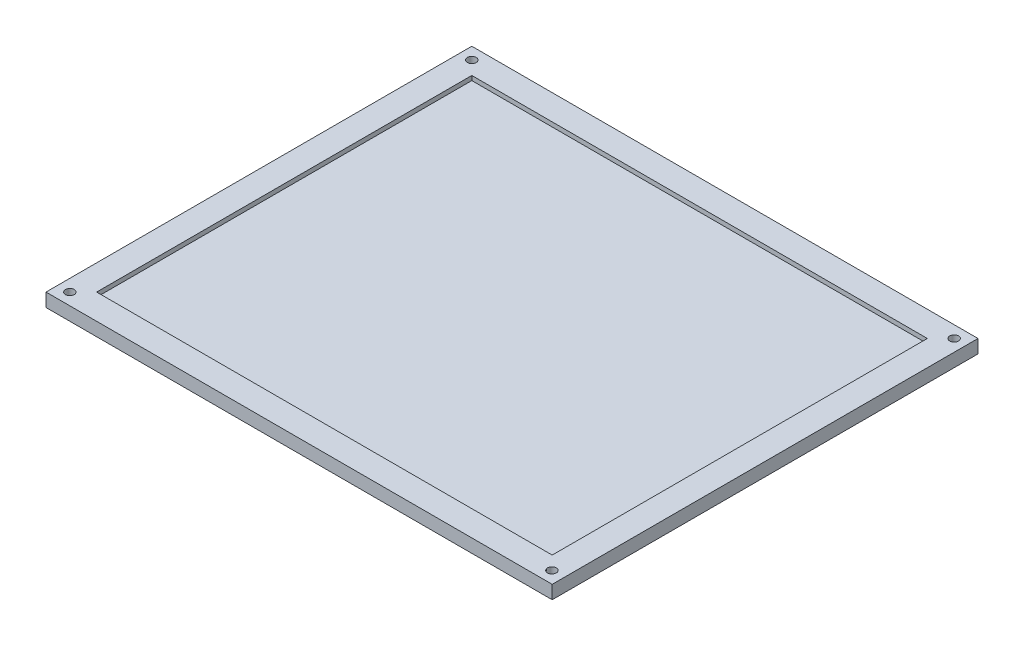
SolidWorks part; units mm, degrees
ref_plane "Front Plane" through (0, 0, 0) normal (0, 0, 1) x (1, 0, 0)
ref_plane "Top Plane" through (0, 0, 0) normal (0, 1, 0) x (1, 0, 0)
ref_plane "Right Plane" through (0, 0, 0) normal (1, 0, 0) x (0, 0, -1)
sketch "Sketch1" plane through (0, 0, 0) normal (0, 1, 0) x (1, 0, 0)
  line L1 (-94.45, 79.45) -> (94.45, 79.45)
  line L2 (-94.45, 79.45) -> (-94.45, -79.45)
  line L3 (-94.45, -79.45) -> (94.45, -79.45)
  line L4 (94.45, 79.45) -> (94.45, -79.45)
  point P4 (0, 79.45)
  point P6 (-94.45, 0)
  dimension "D1" = 158.9
  dimension "D2" = 188.9
extrude "Boss-Extrude1" add sketch "Sketch1" along normal blind 5
sketch "Sketch2" plane through (0, 5, 0) normal (0, 1, 0) x (1, 0, 0)
  line L0 (-94.45, 79.45) -> (-94.45, -79.45) construction
  line L1 (-85, 70) -> (85, 70)
  line L2 (-85, 70) -> (-85, -70)
  line L3 (-85, -70) -> (85, -70)
  line L4 (85, 70) -> (85, -70)
  line L5 (94.45, 79.45) -> (-94.45, 79.45) construction
  point P8 (-85, 0)
  point P10 (0, 70)
  dimension "D1" = 9.45
  dimension "D2" = 9.45
extrude "Cut-Extrude1" cut sketch "Sketch2" against normal blind 1.66
sketch "Sketch3" plane through (0, 5, 0) normal (0, 1, 0) x (1, 0, 0)
  line L0 (-94.45, 79.45) -> (-94.45, -79.45) construction
  line L1 (94.45, 79.45) -> (-94.45, 79.45) construction
  circle A0 centre (-90, 75) radius 1.65
  dimension "D1" = 3.3
  dimension "D2" = 4.45
  dimension "D3" = 4.45
extrude "Cut-Extrude2" cut sketch "Sketch3" against normal blind 5 contours A0
sketch "Sketch6" plane through (0, 5, 0) normal (0, 1, 0) x (1, 0, 0)
  line L0 (-94.45, -79.45) -> (94.45, -79.45) construction
  line L1 (-94.45, 79.45) -> (-94.45, -79.45) construction
  line L2 (94.45, -79.45) -> (94.45, 79.45) construction
  line L3 (94.45, 79.45) -> (-94.45, 79.45) construction
  circle A0 centre (-90, -75) radius 1.65
  circle A1 centre (89.9, -75) radius 1.65
  circle A2 centre (90, 75) radius 1.65
  dimension "D1" = 3.3
  dimension "D6" = 4.45
  dimension "D7" = 4.45
  dimension "D2" = 4.45
  dimension "D3" = 4.45
  dimension "D4" = 4.55
  dimension "D5" = 4.45
extrude "Cut-Extrude4" cut sketch "Sketch6" against normal blind 10
